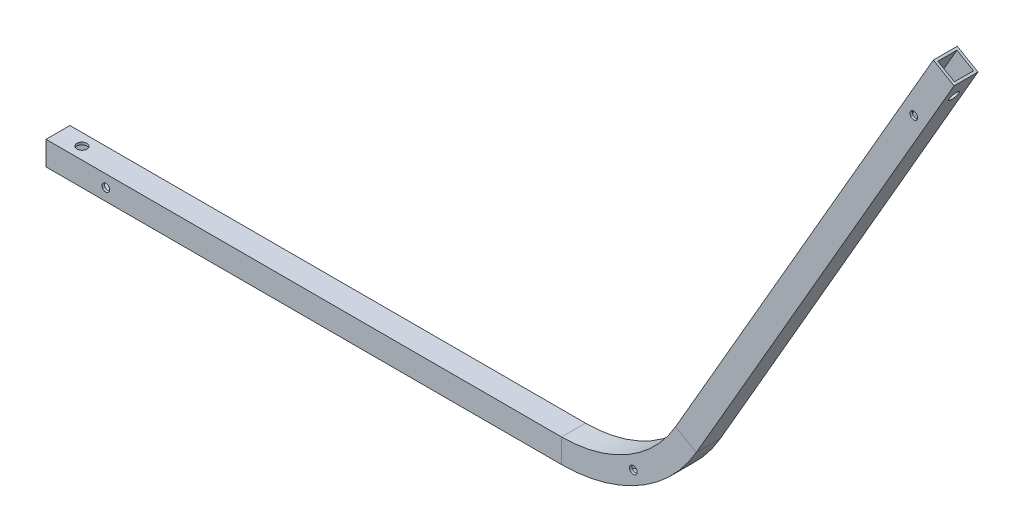
SolidWorks part; units mm, degrees
ref_plane "正面" through (0, 0, 0) normal (0, 0, 1) x (1, 0, 0)
ref_plane "平面" through (0, 0, 0) normal (0, 1, 0) x (1, 0, 0)
ref_plane "右側面" through (0, 0, 0) normal (1, 0, 0) x (0, 0, -1)
sketch "ｽｹｯﾁ2" plane through (0, 0, 0) normal (0, 0, 1) x (1, 0, 0)
  line L0 (0, 0) -> (215.359, 0)
  line L1 (267.3205, 30) -> (375, 216.5064)
  arc A0 (215.359, 0) -> (267.3205, 30) centre (215.359, 60) ccw
  point P6 (250, 0)
  dimension "D4" = 60
  dimension "D1" = 250
  dimension "D2" = 250
  dimension "D3" = 120
sketch "ｽｹｯﾁ3" plane through (0, 0, 0) normal (1, 0, 0) x (0, 0, -1)
  line L0 (4, -4) -> (4, 4)
  line L1 (5, -5) -> (-5, -5)
  line L2 (5, -5) -> (5, 5)
  line L3 (5, 5) -> (-5, 5)
  line L4 (-5, -5) -> (-5, 5)
  line L5 (5, -5) -> (-5, 5) construction
  line L6 (5, 5) -> (-5, -5) construction
  line L7 (4, 4) -> (-4, 4)
  line L8 (-4, -4) -> (-4, 4)
  line L9 (4, -4) -> (-4, -4)
  point P0 (0, 0)
  dimension "D1" = 10
  dimension "D2" = 10
  dimension "D3" = 1
sweep "ｽｲｰﾌﾟ1" add profiles "ｽｹｯﾁ3" path "ｽｹｯﾁ2"
sketch "ｽｹｯﾁ5" plane through (0, 0, 5) normal (0, 0, 1) x (1, 0, 0)
  line L0 (0, 5) -> (0, -5) construction
  line L1 (370.6699, 219.0064) -> (379.3301, 214.0064) construction
  line L2 (262.9904, 32.5) -> (370.6699, 219.0064) construction
  line L3 (242.859, 12.3686) -> (247.859, 3.7083) construction
  circle A0 centre (25, 0) radius 1.6
  circle A1 centre (362.5, 194.8557) radius 1.6
  arc A4 (215.359, 5) -> (262.9904, 32.5) centre (215.359, 60) ccw construction
  arc A5 (215.359, -5) -> (271.6506, 27.5) centre (215.359, 60) ccw construction
  circle A6 centre (245.359, 8.0385) radius 1.6
  dimension "D1" = 25
  dimension "D2" = 3.2
  dimension "D3" = 3.2
  dimension "D4" = 25
  dimension "D5" = 5
  dimension "D6" = 3.2
extrude "ｶｯﾄ - 押し出し2" cut sketch "ｽｹｯﾁ5" against normal blind 10
sketch "ｽｹｯﾁ6" plane through (0, -5, 0) normal (0, -1, 0) x (1, 0, 0)
  line L0 (0, 5) -> (0, -5) construction
  circle A0 centre (10, 0) radius 2.1
  dimension "D1" = 10
  dimension "D2" = 4.2
extrude "ｶｯﾄ - 押し出し3" cut sketch "ｽｹｯﾁ6" against normal blind 10
sketch "ｽｹｯﾁ7" plane through (191.8301, -110.7532, 0) normal (0.866, -0.5, 0) x (0, 0, -1)
  line L0 (-5, 375) -> (5, 375) construction
  circle A0 centre (0, 365) radius 2.1
  dimension "D2" = 4.2
  dimension "D1" = 10
extrude "ｶｯﾄ - 押し出し4" cut sketch "ｽｹｯﾁ7" against normal blind 10
